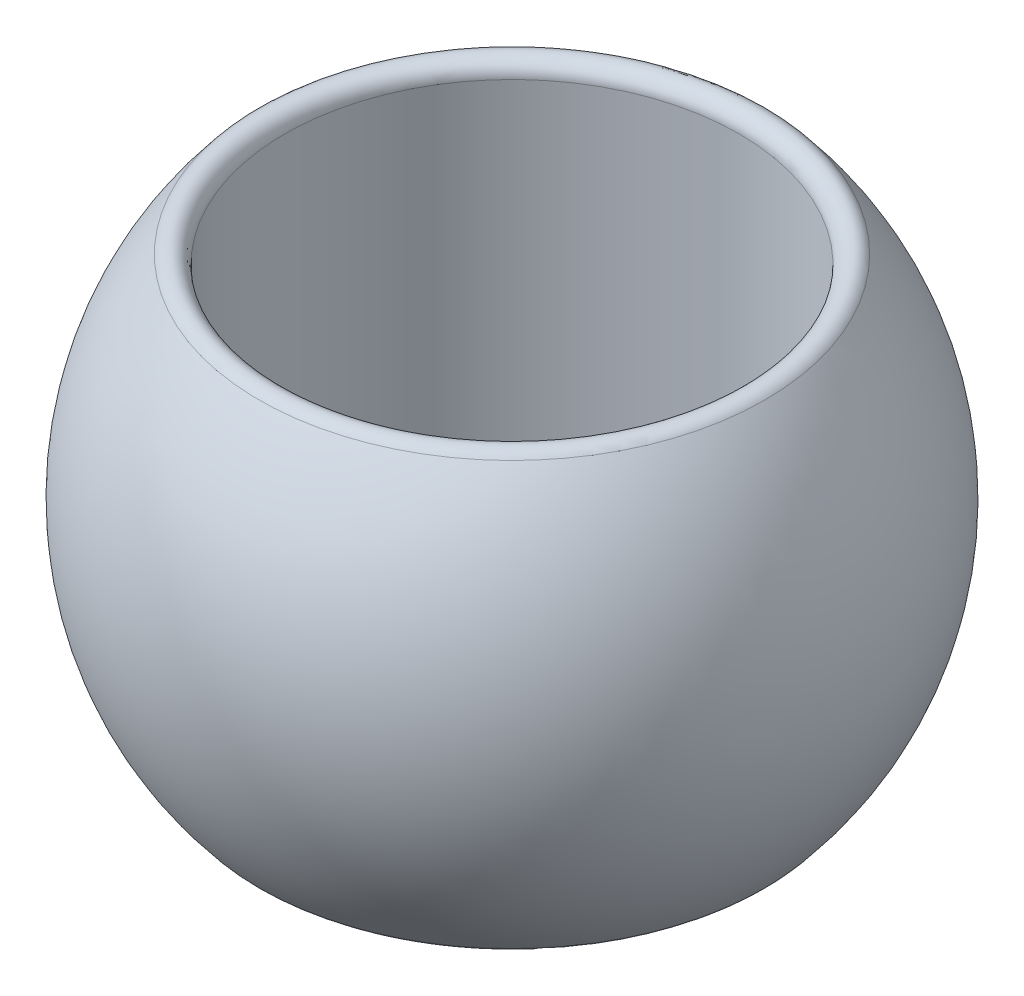
SolidWorks part; units mm, degrees
ref_plane "Front Plane" through (0, 0, 0) normal (0, 0, 1) x (1, 0, 0)
ref_plane "Top Plane" through (0, 0, 0) normal (0, 1, 0) x (1, 0, 0)
ref_plane "Right Plane" through (0, 0, 0) normal (1, 0, 0) x (0, 0, -1)
sketch "Sketch1" plane through (0, 0, 0) normal (0, 0, 1) x (1, 0, 0)
  line L0 (0, 4.5) -> (0, -4.5) construction
  line L1 (0, 4.5) -> (0, -4.5)
  arc A0 (0, -4.5) -> (0, 4.5) centre (0, 0) ccw
  dimension "D1" = 9
revolve "Revolve1" add sketch "Sketch1" angle 360 about L0
sketch "Sketch2" plane through (0, 0, 0) normal (0, 1, 0) x (1, 0, 0)
  circle A0 centre (0, 0) radius 3.1
  dimension "D1" = 6.2
extrude "Cut-Extrude1" cut sketch "Sketch2" against normal blind 10 and the other way blind 10
fillet "Fillet1" radius 0.2 2 edges at (0, 3.2619, -3.1) (0, -3.2619, 3.1)
